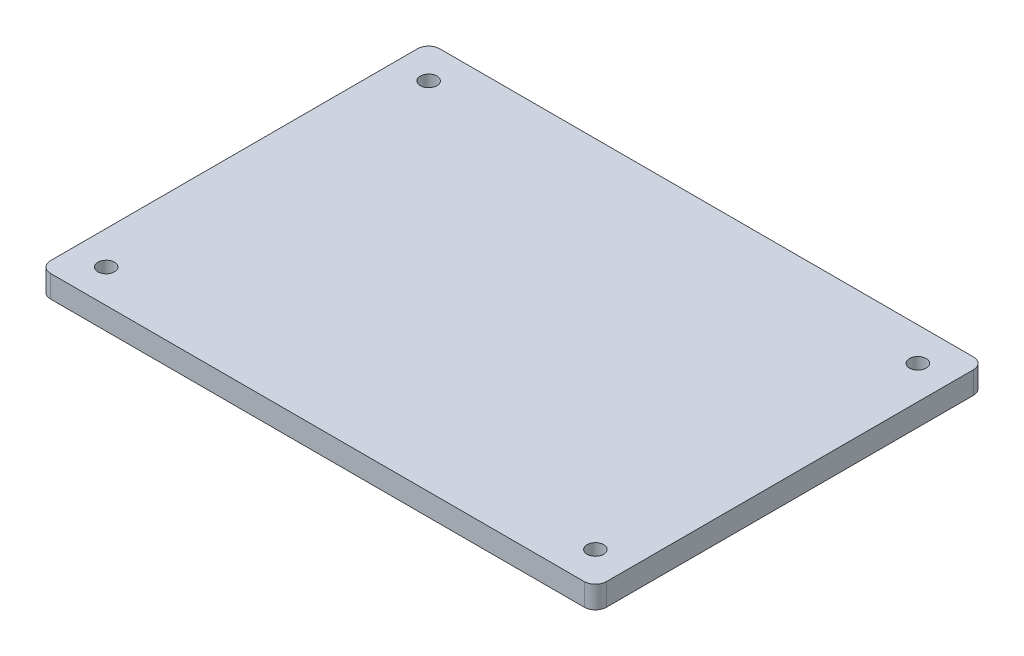
SolidWorks part; units mm, degrees
ref_plane "Alzado" through (0, 0, 0) normal (0, 0, 1) x (1, 0, 0)
ref_plane "Planta" through (0, 0, 0) normal (0, 1, 0) x (1, 0, 0)
ref_plane "Vista lateral" through (0, 0, 0) normal (1, 0, 0) x (0, 0, -1)
sketch "Croquis1" plane through (0, 0, 0) normal (0, 1, 0) x (1, 0, 0)
  line L1 (100, -70) -> (-100, -70)
  line L2 (100, -70) -> (100, 70)
  line L3 (100, 70) -> (-100, 70)
  line L4 (-100, -70) -> (-100, 70)
  line L5 (100, -70) -> (-100, 70) construction
  line L6 (100, 70) -> (-100, -70) construction
  point P0 (0, 0)
  dimension "D1" = 140
  dimension "D2" = 200
extrude "Saliente-Extruir1" add sketch "Croquis1" along normal blind 8
fillet "Redondeo1" radius 4 4 edges at (-100, 4, -70) (100, 4, -70) (100, 4, 70) (-100, 4, 70)
sketch "Croquis2" plane through (0, 8, 0) normal (0, 1, 0) x (1, 0, 0)
  line L0 (96, 70) -> (-96, 70) construction
  line L1 (100, -66) -> (100, 66) construction
  circle A0 centre (88, 58) radius 3
  dimension "D1" = 6
  dimension "D2" = 12
  dimension "D3" = 12
extrude "Cortar-Extruir1" cut sketch "Croquis2" against normal through all
mirror "Simetría1" about plane through (0, 0, 0) normal (0, 0, 1) of "Cortar-Extruir1"
mirror "Simetría2" about plane through (0, 0, 0) normal (1, 0, 0) of "Simetría1"
